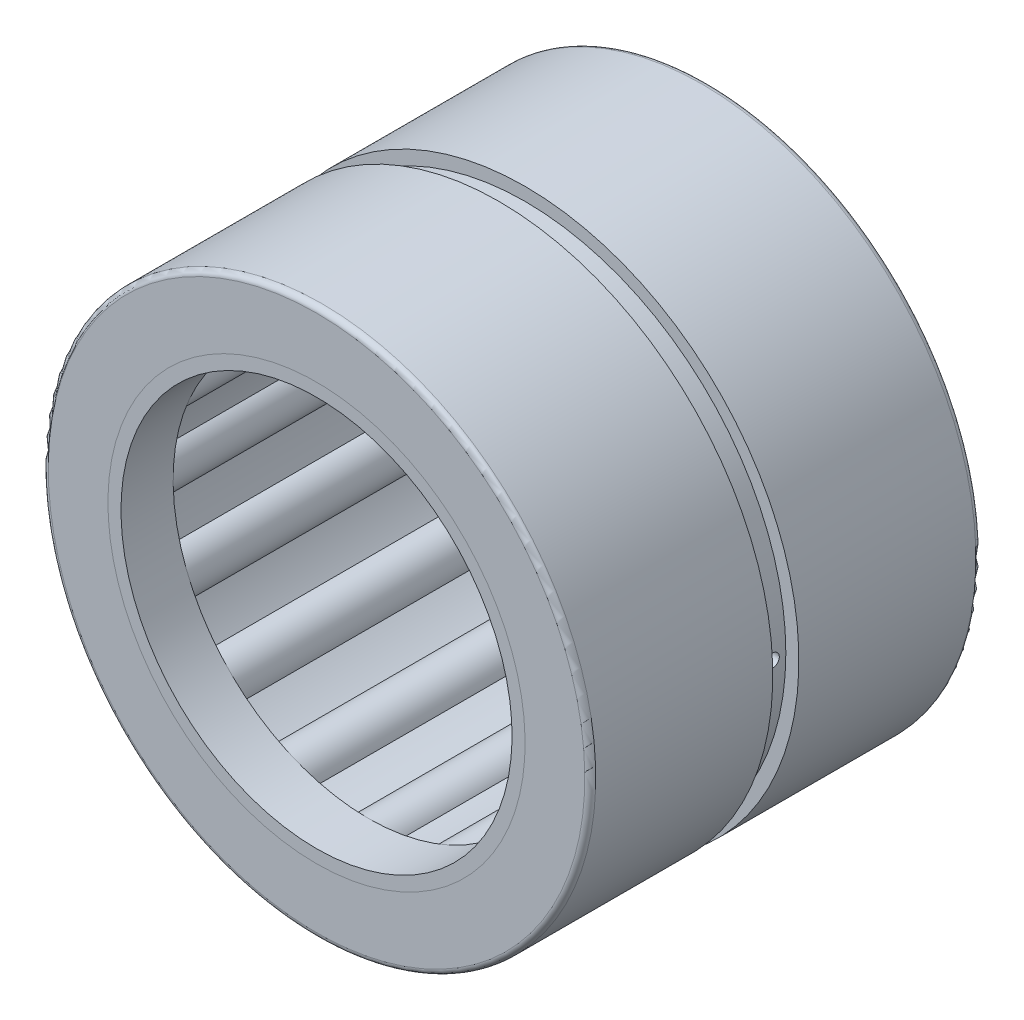
SolidWorks part; units mm, degrees
ref_plane "Front Plane" through (0, 0, 0) normal (0, 0, 1) x (1, 0, 0)
ref_plane "Top Plane" through (0, 0, 0) normal (0, 1, 0) x (1, 0, 0)
ref_plane "Right Plane" through (0, 0, 0) normal (1, 0, 0) x (0, 0, -1)
sketch "Sketch1" plane through (0, 0, 0) normal (1, 0, 0) x (0, 0, -1)
  line L0 (-15.875, 0) -> (15.875, 0) construction
  line L1 (0, 0) -> (0, 22.225) construction
  line L2 (-15.875, 0) -> (-15.875, 22.225) construction
  line L3 (-15.875, 22.225) -> (15.875, 22.225)
  line L4 (15.875, 22.225) -> (15.875, 0) construction
  line L5 (15.875, 0) -> (13.7583, 0) construction
  line L6 (13.7583, 0) -> (13.7583, 20.1083) construction
  line L7 (13.7583, 20.1083) -> (-13.7583, 20.1083)
  line L8 (-13.7583, 20.1083) -> (-13.7583, 0) construction
  line L9 (-13.7583, 0) -> (-15.875, 0) construction
  line L10 (-15.875, 22.225) -> (-15.875, 16.9333)
  line L11 (-15.875, 16.9333) -> (-13.7583, 16.9333)
  line L12 (-13.7583, 16.9333) -> (-13.7583, 20.1083)
  line L13 (13.7583, 22.225) -> (13.7583, 20.1083) construction
  line L14 (13.7583, 20.1083) -> (13.7583, 16.9333)
  line L15 (13.7583, 16.9333) -> (15.875, 16.9333)
  line L16 (15.875, 16.9333) -> (15.875, 22.225)
  line L17 (13.7583, 20.1083) -> (13.7583, 17.9917) construction
  line L18 (13.7583, 17.9917) -> (13.7583, 15.875) construction
  line L19 (13.7583, -20.1083) -> (13.7583, -17.9917) construction
  line L20 (13.7583, -22.225) -> (13.7583, -20.1083) construction
  line L21 (15.875, -16.9333) -> (15.875, -22.225) construction
  line L22 (13.7583, -16.9333) -> (15.875, -16.9333) construction
  line L23 (13.7583, -20.1083) -> (13.7583, -16.9333) construction
  line L24 (-13.7583, -16.9333) -> (-13.7583, -20.1083) construction
  line L25 (-15.875, -16.9333) -> (-13.7583, -16.9333) construction
  line L26 (-15.875, -22.225) -> (-15.875, -16.9333) construction
  line L27 (13.7583, -20.1083) -> (-13.7583, -20.1083) construction
  line L28 (-15.875, -22.225) -> (15.875, -22.225) construction
  point P5 (0, 15.875)
  dimension "Width" = 31.75
  dimension "OD" = 44.45
  dimension "Shaft Dia" = 31.75
revolve "Revolve1" add sketch "Sketch1" angle 360 about L0
sketch "Sketch2" plane through (0, 0, 0) normal (1, 0, 0) x (0, 0, -1)
  line L0 (13.7583, 20.1083) -> (-13.7583, 20.1083) construction
  line L1 (-11.6417, 17.9917) -> (11.6417, 17.9917) construction
  line L2 (-11.6417, 17.9917) -> (-11.6417, 20.1083) construction
  line L3 (-11.6417, 20.1083) -> (11.6417, 20.1083)
  line L4 (11.6417, 17.9917) -> (11.6417, 20.1083) construction
  line L5 (13.7583, 16.9333) -> (15.875, 16.9333) construction
  line L6 (-13.7583, 17.9917) -> (-11.6417, 17.9917) construction
  line L7 (11.6417, 17.9917) -> (13.7583, 17.9917) construction
  line L8 (-15.875, 16.9333) -> (-13.7583, 16.9333) construction
  line L9 (-11.6417, 18.5208) -> (-11.6417, 17.4625) construction
  line L10 (-13.7583, 17.9917) -> (-13.7583, 16.9333) construction
  line L11 (-11.6417, 20.1083) -> (-11.6417, 18.5208)
  line L12 (11.6417, 20.1083) -> (11.6417, 18.5208)
  line L13 (11.6417, 18.5208) -> (-11.6417, 18.5208)
  line L14 (0, 20.1083) -> (0, 15.875) construction
  line L15 (-13.7583, 16.9333) -> (-13.7583, 20.1083) construction
  line L16 (-11.6417, 17.4625) -> (-13.7583, 17.4625) construction
  line L17 (0, 0) -> (15.875, 0) construction
  line L18 (15.875, -22.225) -> (15.875, 22.225) construction
  line L19 (-11.6417, -17.4625) -> (-13.7583, -17.4625) construction
  line L20 (0, -20.1083) -> (0, -15.875) construction
  line L21 (-13.7583, -17.9917) -> (-13.7583, -16.9333) construction
  line L22 (-11.6417, -18.5208) -> (-11.6417, -17.4625) construction
  line L23 (11.6417, -17.9917) -> (13.7583, -17.9917) construction
  line L24 (-13.7583, -17.9917) -> (-11.6417, -17.9917) construction
  line L25 (11.6417, -17.9917) -> (11.6417, -20.1083) construction
  line L26 (-11.6417, -17.9917) -> (-11.6417, -20.1083) construction
  line L27 (-11.6417, -17.9917) -> (11.6417, -17.9917) construction
  line L28 (11.6417, -18.5208) -> (-11.6417, -18.5208) construction
  line L29 (11.6417, -20.1083) -> (11.6417, -18.5208) construction
  line L30 (-11.6417, -20.1083) -> (-11.6417, -18.5208) construction
  line L31 (-11.6417, -20.1083) -> (11.6417, -20.1083) construction
  point P16 (0, 17.9917)
revolve "Revolve2" add sketch "Sketch2" angle 360 about L1
sketch "Sketch3" plane through (0, 0, 0) normal (1, 0, 0) x (0, 0, -1)
  line L0 (13.7583, 20.1083) -> (13.7583, 16.9333) construction
  line L1 (-13.7583, 17.9917) -> (13.7583, 17.9917)
  line L2 (-13.7583, 17.9917) -> (-13.7583, 18.5208)
  line L3 (-13.7583, 18.5208) -> (13.7583, 18.5208)
  line L4 (13.7583, 17.9917) -> (13.7583, 18.5208)
  line L5 (0, 0) -> (15.875, 0) construction
  line L6 (15.875, -22.225) -> (15.875, 22.225) construction
  line L7 (13.7583, -17.9917) -> (13.7583, -18.5208) construction
  line L8 (-13.7583, -18.5208) -> (13.7583, -18.5208) construction
  line L9 (-13.7583, -17.9917) -> (-13.7583, -18.5208) construction
  line L10 (-13.7583, -17.9917) -> (13.7583, -17.9917) construction
revolve "Revolve3" add sketch "Sketch3" angle 360 about L1
ref_axis "Axis1" through (0, 0, -15.875) along (0, 0, 1)
pattern_circular "CirPattern1" count 16 every 22.5 about axis through (0, 0, -15.875) along (0, 0, 1) of bodies 167 166
fillet "Fillet1" radius 0.4445 2 edges at (0, -22.225, -15.875) (0, -22.225, 15.875)
sketch "Sketch4" plane through (0, 0, 0) normal (1, 0, 0) x (0, 0, -1)
  line L0 (-1.0583, 22.225) -> (0, 21.1667)
  line L1 (-15.875, 22.225) -> (15.875, 22.225) construction
  line L2 (0, 0) -> (0, 22.225) construction
  line L3 (0, 21.1667) -> (1.0583, 22.225)
  line L4 (1.0583, 22.225) -> (-1.0583, 22.225)
  line L5 (0, 22.225) -> (0, 20.1083) construction
revolve "Cut-Revolve1" cut sketch "Sketch4" angle 360 about L0
sketch "Sketch5" plane through (0, 0, 0) normal (1, 0, 0) x (0, 0, -1)
  line L0 (15.875, 22.225) -> (15.875, 0) construction
  line L1 (15.875, 15.875) -> (11.6417, 15.875)
  line L2 (15.875, 15.875) -> (15.875, 16.9333)
  line L3 (15.875, 16.9333) -> (11.6417, 16.9333)
  line L4 (11.6417, 15.875) -> (11.6417, 16.9333)
  line L5 (-15.875, 0) -> (-15.875, 22.225) construction
  line L6 (-15.875, 15.875) -> (-11.6417, 15.875)
  line L7 (-15.875, 15.875) -> (-15.875, 16.9333)
  line L8 (-15.875, 16.9333) -> (-11.6417, 16.9333)
  line L9 (-11.6417, 15.875) -> (-11.6417, 16.9333)
  line L10 (-11.6417, 20.1083) -> (-11.6417, 18.5208) construction
  line L11 (-15.875, 16.9333) -> (-13.7583, 16.9333) construction
revolve "Revolve4" add sketch "Sketch5" angle 360 about L0
sketch "Sketch7" plane through (0, 0, -11.6417) normal (0, 0, 1) x (1, 0, 0)
  circle A0 centre (0, 0) radius 16.9333 construction
  circle A2 centre (0, 0) radius 16.9333
  circle A3 centre (0, 0) radius 20.1083 construction
  circle A4 centre (0, 0) radius 20.1083 construction
  circle A5 centre (0, 0) radius 20.3623
  dimension "D1" = 0.254
extrude "Boss-Extrude1" add sketch "Sketch7" along normal up to surface (25.4 mm away) separate body up to face at (0, -20.1083, 13.7583)
revolve "Cut-Revolve2" cut sketch "Sketch2<2>" angle 360 about L1
sketch "Sketch2<2>" plane through (0, 0, 0) normal (1, 0, 0) x (0, 0, -1) same geometry as "Sketch2"
pattern_circular "CirPattern2" count 16 over 360 about axis through (0, 0, 15.875) along (0, 0, 1) of "Cut-Revolve2"
sketch "Sketch8" plane through (0, 0, 0) normal (1, 0, 0) x (0, 0, -1)
  line L0 (-1.0583, 22.225) -> (-1.0583, 21.1667)
  line L1 (-1.0583, -22.225) -> (-1.0583, 22.225) construction
  line L2 (-1.0583, 21.1667) -> (1.0583, 21.1667)
  line L3 (1.0583, -22.225) -> (1.0583, 22.225) construction
  line L4 (1.0583, 21.1667) -> (1.0583, 22.225)
  line L5 (1.0583, 22.225) -> (-1.0583, 22.225)
  dimension "D1" = 2.1167
revolve "Cut-Revolve3" cut sketch "Sketch8" angle 360 about axis through (0, 0, 15.875) along (0, 0, 1)
sketch "Sketch9" plane through (0, 0, 0) normal (1, 0, 0) x (0, 0, -1)
  circle A0 centre (0, 0) radius 0.5292
extrude "Cut-Extrude1" cut sketch "Sketch9" along normal through all
equation "\"Angle@CirPattern1\" = 360/\"Rollers@CirPattern1\""
equation "\"Rollers@CirPattern1\" = \"OD@Sketch1\"*9"
equation "\"D1@Fillet1\" = \"OD@Sketch1\"*.01"
equation "\"D1@CirPattern2\"= \"Rollers@CirPattern1\""
equation "\"D1@Sketch9\"= \"D1@Sketch8\" * .5"
